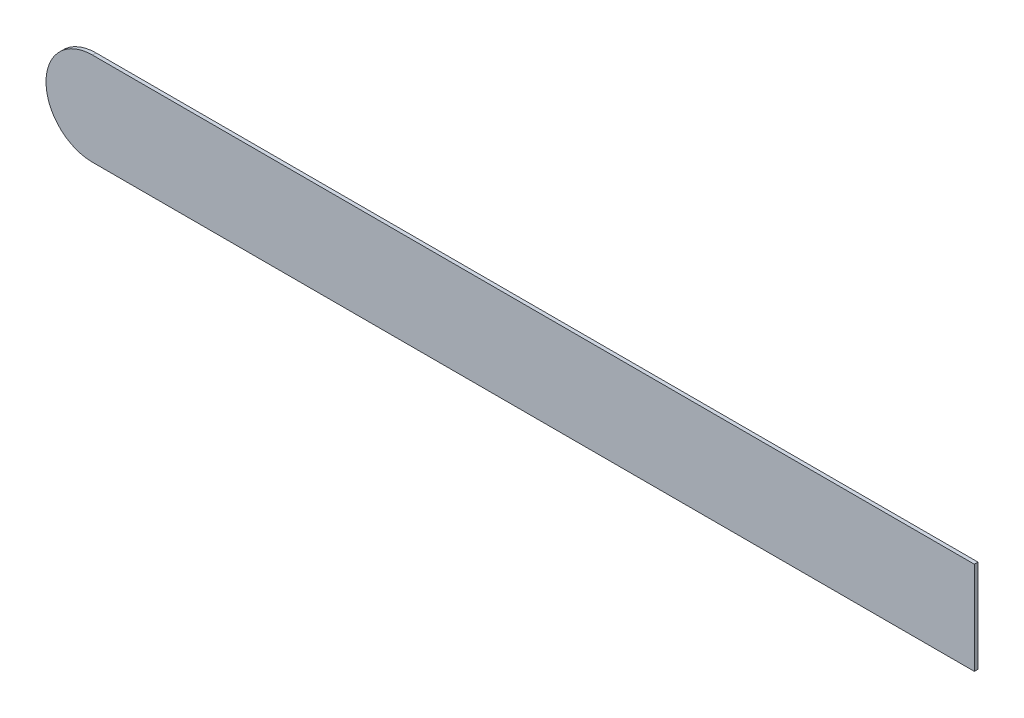
SolidWorks part; units mm, degrees
material "Chrome Stainless Steel"
ref_plane "front" through (0, 0, 0) normal (0, 0, 1) x (1, 0, 0)
ref_plane "top" through (0, 0, 0) normal (0, 1, 0) x (1, 0, 0)
ref_plane "right" through (0, 0, 0) normal (1, 0, 0) x (0, 0, -1)
sketch "Sketch1" plane through (0, 0, 0) normal (0, 1, 0) x (1, 0, 0)
  line L0 (-37.3893, 0) -> (34.3302, 0) construction
  line L1 (0, 32.2908) -> (0, -25.4927) construction
  line L3 (-63.5, -0.25) -> (63.5, -0.25)
  line L4 (-63.5, -0.25) -> (-63.5, 0.25)
  line L5 (-63.5, 0.25) -> (63.5, 0.25)
  line L6 (63.5, -0.25) -> (63.5, 0.25)
  dimension "D1" = 0.5
  dimension "D2" = 127
extrude "Base-Extrude" add sketch "Sketch1" along normal mid plane 12.7
fillet "Fillet1" radius 6.35 2 edges at (-63.5, 6.35, 0) (-63.5, -6.35, 0)
